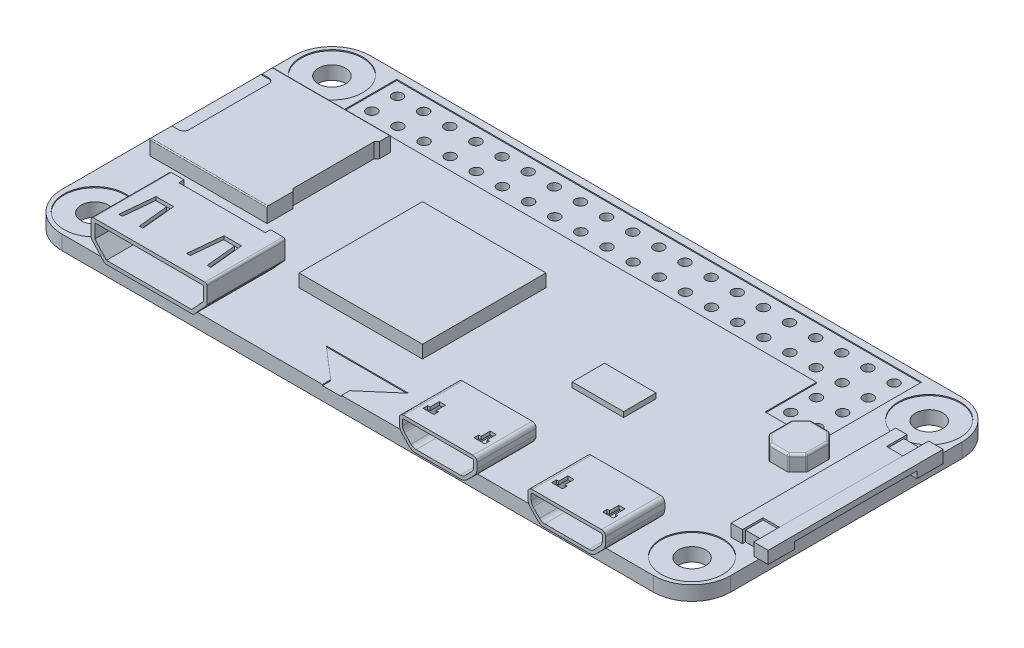
SolidWorks part; units mm, degrees
ref_plane "Front Plane" through (0, 0, 0) normal (0, 0, 1) x (1, 0, 0)
ref_plane "Top Plane" through (0, 0, 0) normal (0, 1, 0) x (1, 0, 0)
ref_plane "Right Plane" through (0, 0, 0) normal (1, 0, 0) x (0, 0, -1)
sketch "Sketch1" plane through (0, 0, 0) normal (0, 1, 0) x (1, 0, 0)
  line L1 (-28.75, 15) -> (28.75, 15)
  line L2 (-32.5, 11.25) -> (-32.5, -11.25)
  line L3 (-28.75, -15) -> (28.75, -15)
  line L4 (32.5, 11.25) -> (32.5, -11.25)
  line L5 (-32.5, 15) -> (32.5, -15) construction
  line L6 (-32.5, -15) -> (32.5, 15) construction
  arc A0 (-32.5, -11.25) -> (-28.75, -15) centre (-28.75, -11.25) ccw
  arc A1 (28.75, -15) -> (32.5, -11.25) centre (28.75, -11.25) ccw
  arc A2 (28.75, 15) -> (32.5, 11.25) centre (28.75, 11.25) cw
  arc A3 (-28.75, 15) -> (-32.5, 11.25) centre (-28.75, 11.25) ccw
  point P0 (0, 0)
  dimension "D3" = 3.75
  dimension "D1" = 65
  dimension "D2" = 30
extrude "Boss-Extrude1" add sketch "Sketch1" along normal blind 1.4 contours L1 A2 L4 A1 L3 A0 L2 A3
sketch "Sketch2" plane through (0, 1.4, 0) normal (0, 1, 0) x (1, 0, 0)
  line L0 (0, 15) -> (0, -15) construction
  line L1 (-28.75, 15) -> (28.75, 15) construction
  line L2 (-28.75, -15) -> (28.75, -15) construction
  line L3 (-32.5, 0) -> (32.5, 0) construction
  line L4 (-32.5, 11.25) -> (-32.5, -11.25) construction
  line L5 (32.5, 11.25) -> (32.5, -11.25) construction
  circle A0 centre (-29.025, 11.525) radius 1.325
  circle A2 centre (29.025, 11.525) radius 1.325
  circle A3 centre (29.025, -11.525) radius 1.325
  circle A4 centre (-29.025, -11.525) radius 1.325
  dimension "D1" = 2.65
  dimension "D2" = 2.15
  dimension "D3" = 2.15
extrude "Cut-Extrude1" cut sketch "Sketch2" against normal through all
sketch "Sketch3" plane through (0, 1.4, 0) normal (0, 1, 0) x (1, 0, 0)
  line L0 (-24.128, 13) -> (-24.128, 10.5) construction
  line L3 (-28.75, 15) -> (28.75, 15) construction
  line L5 (-32.5, 11.25) -> (-32.5, -11.25) construction
  circle A0 centre (-24.128, 13) radius 0.5
  circle A1 centre (-24.128, 10.5) radius 0.5
  dimension "D1" = 1
  dimension "D3" = 1.5
  dimension "D4" = 7.872
  dimension "D2" = 2.5
extrude "Cut-Extrude2" cut sketch "Sketch3" against normal through all
pattern_linear "LPattern1" count 20 spacing 2.54 along (1, 0, 0) of "Cut-Extrude2"
sketch "Sketch5" plane through (0, 1.4, 0) normal (0, 1, 0) x (1, 0, 0)
  line L0 (21.592, 10.5) -> (21.592, 5.5) construction
  line L1 (24.132, 10.5) -> (24.132, 5.5) construction
  line L2 (24.132, 5.5) -> (21.592, 5.5) construction
  circle A0 centre (21.592, 5.5) radius 0.5
  circle A1 centre (24.132, 5.5) radius 0.5
  circle A2 centre (21.592, 8) radius 0.5
  circle A3 centre (24.132, 8) radius 0.5
  dimension "D1" = 2.5
  dimension "D2" = 1
extrude "Cut-Extrude4" cut sketch "Sketch5" against normal through all
sketch "Sketch4" plane through (0, 1.4, 0) normal (0, 1, 0) x (1, 0, 0)
  line L0 (0, 0) -> (0, 14.3) construction
  line L1 (-24.128, 13) -> (-24.128, 10.5) construction
  line L2 (-25.5, 14.3) -> (25.5, 14.3)
  line L3 (-25.5, 14.3) -> (-25.5, 9.2)
  line L4 (-25.5, 9.2) -> (20.4, 9.2)
  line L5 (25.5, 14.3) -> (25.5, 9.2)
  line L6 (-25.5, 11.75) -> (-24.128, 11.75) construction
  line L7 (20.4, 9.2) -> (25.5, 9.2) construction
  line L8 (-2.5, -15) -> (-2.5, -11.55) construction
  line L9 (25.5, 9.2) -> (25.5, 4.2)
  line L10 (25.5, 4.2) -> (20.4, 4.2)
  line L11 (20.4, 9.2) -> (20.4, 4.2)
  line L12 (-28.75, -15) -> (28.75, -15) construction
  line L13 (-6.5, -11.55) -> (1.5, -11.55)
  line L14 (1.5, -11.55) -> (-1.575, -14.2)
  line L15 (-1.575, -14.2) -> (-1.575, -15)
  line L16 (-1.575, -15) -> (-3.425, -15)
  line L17 (-3.425, -15) -> (-3.425, -14.2)
  line L18 (-3.425, -14.2) -> (-6.5, -11.55)
  line L19 (-32.5, 11.25) -> (-32.5, -11.25) construction
  circle A0 centre (-29.025, 11.525) radius 3
  circle A1 centre (-29.025, -11.525) radius 3
  circle A2 centre (29.025, -11.525) radius 3
  circle A3 centre (29.025, 11.525) radius 3
  point P23 (-24.128, 11.75)
  point P26 (-25.5, 11.75)
  dimension "D1" = 6
  dimension "D2" = 5.1
  dimension "D3" = 51
  dimension "D4" = 5.1
  dimension "D5" = 5
  dimension "D6" = 8
  dimension "D7" = 1.85
  dimension "D8" = 3.45
  dimension "D9" = 0.8
  dimension "D10" = 30
extrude "Cut-Extrude3" cut sketch "Sketch4" against normal blind 0.1
sketch "Sketch6" plane through (0, 1.4, 0) normal (0, 1, 0) x (1, 0, 0)
  line L0 (-28.75, -15) -> (-3.425, -15) construction
  line L1 (-12.7, 4) -> (-0.7, 4)
  line L2 (-12.7, 4) -> (-12.7, -8)
  line L3 (-12.7, -8) -> (-0.7, -8)
  line L4 (-0.7, 4) -> (-0.7, -8)
  line L5 (-12.7, 4) -> (-0.7, -8) construction
  line L6 (-12.7, -8) -> (-0.7, 4) construction
  line L7 (-32.5, 11.25) -> (-32.5, -11.25) construction
  point P0 (-6.7, -2)
  dimension "D1" = 12
  dimension "D2" = 7
  dimension "D3" = 19.8
extrude "Boss-Extrude2" add sketch "Sketch6" along normal blind 1.25
sketch "Sketch7" plane through (0, 1.4, 0) normal (0, 1, 0) x (1, 0, 0)
  line L0 (-19.65, 7.85) -> (-19.65, 6.75)
  line L1 (-31.05, 7.85) -> (-19.65, 7.85)
  line L2 (-31.05, 7.85) -> (-31.05, -4.15) construction
  line L3 (-31.05, -4.15) -> (-19.65, -4.15)
  line L4 (-19.65, 7.85) -> (-19.65, -4.15) construction
  line L5 (-19.65, 6.75) -> (-19.9, 6.5)
  line L6 (-19.9, 6.5) -> (-19.9, -1.4)
  line L7 (-19.9, -1.4) -> (-19.65, -1.65)
  line L8 (-19.65, -1.65) -> (-19.65, -4.15)
  line L9 (-31.05, 7.85) -> (-31.05, 6.75)
  line L10 (-31.05, 6.75) -> (-30.4, 6.75)
  line L11 (-29.9, 6.25) -> (-29.9, -1.5)
  line L12 (-30.4, -2) -> (-31.05, -2)
  line L13 (-31.05, -2) -> (-31.05, -4.15)
  line L14 (-28.75, 15) -> (28.75, 15) construction
  line L15 (-32.5, 11.25) -> (-32.5, -11.25) construction
  arc A0 (-29.9, -1.5) -> (-30.4, -2) centre (-30.4, -1.5) cw
  arc A1 (-30.4, 6.75) -> (-29.9, 6.25) centre (-30.4, 6.25) cw
  dimension "D9" = 0.5
  dimension "D1" = 11.4
  dimension "D2" = 12
  dimension "D3" = 2.5
  dimension "D4" = 1.1
  dimension "D5" = 0.25
  dimension "D6" = 1.1
  dimension "D7" = 2.15
  dimension "D8" = 1.15
  dimension "D10" = 7.15
  dimension "D11" = 1.45
extrude "Boss-Extrude3" add sketch "Sketch7" along normal blind 1.45
fillet "Fillet2" radius 0.1 2 edges at (-25.35, 2.85, -7.85) (-25.35, 2.85, 4.15)
sketch "Sketch8" plane through (-29.9, 0, 0) normal (-1, 0, 0) x (0, 0, 1)
  line L0 (-7.85, 2.75) -> (-7.85, 1.4) construction
  line L1 (-7.75, 2.75) -> (4.05, 2.75)
  line L2 (-7.75, 2.75) -> (-7.75, 1.5)
  line L3 (-7.75, 1.5) -> (4.05, 1.5)
  line L4 (4.05, 2.75) -> (4.05, 1.5)
  line L5 (-6.25, 2.85) -> (1.5, 2.85) construction
  line L6 (4.15, 2.75) -> (4.15, 1.4) construction
  line L7 (-6.25, 1.4) -> (1.5, 1.4) construction
  dimension "D1" = 0.1
  dimension "D2" = 0.1
  dimension "D3" = 0.1
  dimension "D4" = 0.1
extrude "Cut-Extrude5" cut sketch "Sketch8" against normal blind 9.5 and the other way through all
sketch "Sketch9" plane through (0, 0, 15) normal (0, 0, 1) x (1, 0, 0)
  line L0 (-19.875, 1.4) -> (-19.875, 4.7) construction
  line L1 (-28.75, 1.4) -> (-3.425, 1.4) construction
  line L2 (-25.5, 4.7) -> (-14.25, 4.7)
  line L3 (-14.25, 4.7) -> (-14.25, 2.85)
  line L4 (-14.25, 2.85) -> (-15.575, 1.4)
  line L5 (-12.7, 1.4) -> (-0.7, 1.4) construction
  line L6 (-15.575, 1.4) -> (-24.175, 1.4)
  line L7 (-24.175, 1.4) -> (-25.5, 2.85)
  line L8 (-25.5, 2.85) -> (-25.5, 4.7)
  line L9 (-32.5, 1.4) -> (-32.5, 0) construction
  dimension "D1" = 3.3
  dimension "D2" = 1.85
  dimension "D3" = 8.6
  dimension "D4" = 11.25
  dimension "D5" = 7
extrude "Boss-Extrude4" add sketch "Sketch9" along normal blind 0.4 and the other way blind 7.2 separate body
fillet "Fillet1" radius 0.2 6 edges at (-15.575, 1.4, 11.6) (-24.175, 1.4, 11.6) (-25.5, 2.85, 11.6) (-14.25, 2.85, 11.6) (-25.5, 4.7, 11.6) (-14.25, 4.7, 11.6)
sketch "Sketch10" plane through (0, 0, 15.4) normal (0, 0, 1) x (1, 0, 0)
  line L12 (-25.15, 4.35) -> (-25.15, 2.9858)
  line L13 (-25.15, 2.9858) -> (-24.0207, 1.75)
  line L14 (-24.0207, 1.75) -> (-15.7293, 1.75)
  line L15 (-15.7293, 1.75) -> (-14.6, 2.9858)
  line L16 (-14.6, 2.9858) -> (-14.6, 4.35)
  line L17 (-14.6, 4.35) -> (-25.15, 4.35)
  line L18 (-25.15, 4.35) -> (-25.15, 2.9858)
  line L19 (-25.15, 2.9858) -> (-24.0207, 1.75)
  line L20 (-24.0207, 1.75) -> (-15.7293, 1.75)
  line L21 (-15.7293, 1.75) -> (-14.6, 2.9858)
  line L22 (-14.6, 2.9858) -> (-14.6, 4.35)
  line L23 (-14.6, 4.35) -> (-25.15, 4.35)
  dimension "D1" = 0.35
extrude "Cut-Extrude6" cut sketch "Sketch10" against normal blind 7
sketch "Sketch11" plane through (0, 0, 8.4) normal (0, 0, 1) x (1, 0, 0)
  line L0 (-19.875, 3.5) -> (-19.875, 1.75) construction
  line L1 (-23.375, 2.95) -> (-16.375, 2.95)
  line L2 (-23.375, 2.95) -> (-23.375, 3.5)
  line L3 (-23.375, 3.5) -> (-16.375, 3.5)
  line L4 (-16.375, 2.95) -> (-16.375, 3.5)
  line L5 (-24.0207, 1.75) -> (-15.7293, 1.75) construction
  line L6 (-24.0207, 1.75) -> (-15.7293, 1.75) construction
  dimension "D1" = 7
  dimension "D2" = 0.55
  dimension "D3" = 1.2
extrude "Boss-Extrude5" add sketch "Sketch11" along normal blind 3.5
sketch "Sketch12" plane through (0, 4.35, 0) normal (0, -1, 0) x (1, 0, 0)
  line L0 (-19.875, 7.8) -> (-19.875, 15.4) construction
  line L1 (-14.45, 7.8) -> (-25.3, 7.8) construction
  line L2 (-14.45, 15.4) -> (-25.3, 15.4) construction
  line L3 (-23.175, 10.57) -> (-23.175, 13.4458) construction
  line L4 (-24.025, 10.57) -> (-22.325, 10.57)
  line L5 (-22.325, 10.57) -> (-22, 13.87)
  line L6 (-22, 13.87) -> (-22.3517, 13.87)
  line L7 (-22.3517, 13.87) -> (-22.6422, 10.92)
  line L8 (-22.6422, 10.92) -> (-23.7078, 10.92)
  line L9 (-23.9983, 13.87) -> (-23.7078, 10.92)
  line L10 (-24.35, 13.87) -> (-23.9983, 13.87)
  line L11 (-24.025, 10.57) -> (-24.35, 13.87)
  line L12 (-16.575, 10.57) -> (-16.575, 13.4458) construction
  line L13 (-15.725, 10.57) -> (-15.4, 13.87)
  line L14 (-15.4, 13.87) -> (-15.7517, 13.87)
  line L15 (-15.7517, 13.87) -> (-16.0422, 10.92)
  line L16 (-17.1078, 10.92) -> (-16.0422, 10.92)
  line L17 (-17.3983, 13.87) -> (-17.1078, 10.92)
  line L18 (-17.75, 13.87) -> (-17.3983, 13.87)
  line L19 (-17.425, 10.57) -> (-17.75, 13.87)
  line L20 (-15.725, 10.57) -> (-17.425, 10.57)
  point P15 (-23.175, 10.92)
  point P28 (-16.575, 10.92)
  dimension "D1" = 0.35
  dimension "D2" = 0.35
  dimension "D3" = 3.3
  dimension "D4" = 2.35
  dimension "D5" = 1.7
  dimension "D6" = 2.77
  dimension "D7" = 4.25
extrude "Cut-Extrude7" cut sketch "Sketch12" against normal through all
sketch "Sketch13" plane through (0, 0, 7.8) normal (0, 0, -1) x (-1, 0, 0)
  line L0 (14.45, 4.7) -> (25.3, 4.7) construction
  line L1 (15.675, 4.7) -> (24.075, 4.7)
  line L2 (15.675, 4.7) -> (15.675, 3.3)
  line L3 (15.675, 3.3) -> (24.075, 3.3)
  line L4 (24.075, 4.7) -> (24.075, 3.3)
  line L5 (19.875, 1.4) -> (19.875, 4.7) construction
  line L6 (24.0868, 1.4) -> (15.6632, 1.4) construction
  dimension "D1" = 8.4
  dimension "D2" = 1.4
extrude "Cut-Extrude8" cut sketch "Sketch13" against normal blind 0.5
sketch "Sketch15" plane through (0, 0, 15) normal (0, 0, 1) x (1, 0, 0)
  line L0 (21.575, 1.4) -> (21.575, 4) construction
  line L1 (-1.575, 1.4) -> (28.75, 1.4) construction
  line L2 (18.2, 4) -> (24.95, 4)
  line L3 (25.35, 3.6) -> (25.35, 3.0523)
  line L4 (25.0714, 2.3598) -> (24.4452, 1.7075)
  line L5 (23.7238, 1.4) -> (19.4262, 1.4)
  line L6 (32.5, 1.4) -> (32.5, 0) construction
  line L7 (18.0786, 2.3598) -> (18.7048, 1.7075)
  line L8 (17.8, 3.6) -> (17.8, 3.0523)
  line L9 (15.325, 0) -> (15.325, 5.5788) construction
  line L10 (-28.75, 0) -> (28.75, 0) construction
  line L11 (9.075, 1.4) -> (9.075, 4) construction
  line L12 (12.85, 3.6) -> (12.85, 3.0523)
  line L13 (12.5714, 2.3598) -> (11.9452, 1.7075)
  line L14 (6.9262, 1.4) -> (11.2238, 1.4)
  line L15 (5.5786, 2.3598) -> (6.2048, 1.7075)
  line L16 (5.3, 3.6) -> (5.3, 3.0523)
  line L17 (12.45, 4) -> (5.7, 4)
  arc A0 (24.4452, 1.7075) -> (23.7238, 1.4) centre (23.7238, 2.4) cw
  arc A1 (18.7048, 1.7075) -> (19.4262, 1.4) centre (19.4262, 2.4) ccw
  arc A2 (25.35, 3.0523) -> (25.0714, 2.3598) centre (24.35, 3.0523) cw
  arc A3 (18.0786, 2.3598) -> (17.8, 3.0523) centre (18.8, 3.0523) cw
  arc A4 (24.95, 4) -> (25.35, 3.6) centre (24.95, 3.6) cw
  arc A5 (17.8, 3.6) -> (18.2, 4) centre (18.2, 3.6) cw
  arc A6 (12.85, 3.6) -> (12.45, 4) centre (12.45, 3.6) ccw
  arc A7 (5.7, 4) -> (5.3, 3.6) centre (5.7, 3.6) ccw
  arc A8 (12.5714, 2.3598) -> (12.85, 3.0523) centre (11.85, 3.0523) ccw
  arc A9 (5.3, 3.0523) -> (5.5786, 2.3598) centre (6.3, 3.0523) ccw
  arc A10 (11.9452, 1.7075) -> (11.2238, 1.4) centre (11.2238, 2.4) cw
  arc A11 (6.2048, 1.7075) -> (6.9262, 1.4) centre (6.9262, 2.4) ccw
  point P14 (24.15, 1.4)
  point P17 (19, 1.4)
  point P20 (25.35, 2.65)
  point P23 (17.8, 2.65)
  point P26 (25.35, 4)
  point P29 (17.8, 4)
  point P54 (12.85, 4)
  point P55 (5.3, 4)
  point P56 (12.85, 2.65)
  point P57 (5.3, 2.65)
  point P58 (11.65, 1.4)
  point P59 (6.5, 1.4)
  dimension "D6" = 1
  dimension "D7" = 0.4
  dimension "D1" = 7.55
  dimension "D2" = 2.6
  dimension "D3" = 1.35
  dimension "D4" = 5.15
  dimension "D5" = 7.15
  dimension "D8" = 4.95
extrude "Boss-Extrude6" add sketch "Sketch15" along normal blind 1.25 and the other way blind 4.5
sketch "Sketch16" plane through (0, 0, 16.25) normal (0, 0, 1) x (1, 0, 0)
  line L12 (12.45, 3.68) -> (5.7, 3.68)
  line L13 (5.62, 3.6) -> (5.62, 3.0523)
  line L14 (5.8095, 2.5814) -> (6.4357, 1.9291)
  line L15 (6.9262, 1.72) -> (11.2238, 1.72)
  line L16 (11.7143, 1.9291) -> (12.3405, 2.5814)
  line L17 (12.53, 3.0523) -> (12.53, 3.6)
  line L18 (12.45, 3.68) -> (5.7, 3.68)
  line L19 (5.62, 3.6) -> (5.62, 3.0523)
  line L20 (5.8095, 2.5814) -> (6.4357, 1.9291)
  line L21 (6.9262, 1.72) -> (11.2238, 1.72)
  line L22 (11.7143, 1.9291) -> (12.3405, 2.5814)
  line L23 (12.53, 3.0523) -> (12.53, 3.6)
  line L30 (24.2143, 1.9291) -> (24.8405, 2.5814)
  line L31 (25.03, 3.0523) -> (25.03, 3.6)
  line L32 (24.95, 3.68) -> (18.2, 3.68)
  line L33 (18.12, 3.6) -> (18.12, 3.0523)
  line L34 (18.3095, 2.5814) -> (18.9357, 1.9291)
  line L35 (19.4262, 1.72) -> (23.7238, 1.72)
  line L36 (24.2143, 1.9291) -> (24.8405, 2.5814)
  line L37 (25.03, 3.0523) -> (25.03, 3.6)
  line L38 (24.95, 3.68) -> (18.2, 3.68)
  line L39 (18.12, 3.6) -> (18.12, 3.0523)
  line L40 (18.3095, 2.5814) -> (18.9357, 1.9291)
  line L41 (19.4262, 1.72) -> (23.7238, 1.72)
  arc A12 (12.53, 3.6) -> (12.45, 3.68) centre (12.45, 3.6) ccw
  arc A13 (5.7, 3.68) -> (5.62, 3.6) centre (5.7, 3.6) ccw
  arc A14 (5.62, 3.0523) -> (5.8095, 2.5814) centre (6.3, 3.0523) ccw
  arc A15 (6.4357, 1.9291) -> (6.9262, 1.72) centre (6.9262, 2.4) ccw
  arc A16 (11.2238, 1.72) -> (11.7143, 1.9291) centre (11.2238, 2.4) ccw
  arc A17 (12.3405, 2.5814) -> (12.53, 3.0523) centre (11.85, 3.0523) ccw
  arc A18 (12.53, 3.6) -> (12.45, 3.68) centre (12.45, 3.6) ccw
  arc A19 (5.7, 3.68) -> (5.62, 3.6) centre (5.7, 3.6) ccw
  arc A20 (5.62, 3.0523) -> (5.8095, 2.5814) centre (6.3, 3.0523) ccw
  arc A21 (6.4357, 1.9291) -> (6.9262, 1.72) centre (6.9262, 2.4) ccw
  arc A22 (11.2238, 1.72) -> (11.7143, 1.9291) centre (11.2238, 2.4) ccw
  arc A23 (12.3405, 2.5814) -> (12.53, 3.0523) centre (11.85, 3.0523) ccw
  arc A30 (23.7238, 1.72) -> (24.2143, 1.9291) centre (23.7238, 2.4) ccw
  arc A31 (24.8405, 2.5814) -> (25.03, 3.0523) centre (24.35, 3.0523) ccw
  arc A32 (25.03, 3.6) -> (24.95, 3.68) centre (24.95, 3.6) ccw
  arc A33 (18.2, 3.68) -> (18.12, 3.6) centre (18.2, 3.6) ccw
  arc A34 (18.12, 3.0523) -> (18.3095, 2.5814) centre (18.8, 3.0523) ccw
  arc A35 (18.9357, 1.9291) -> (19.4262, 1.72) centre (19.4262, 2.4) ccw
  arc A36 (23.7238, 1.72) -> (24.2143, 1.9291) centre (23.7238, 2.4) ccw
  arc A37 (24.8405, 2.5814) -> (25.03, 3.0523) centre (24.35, 3.0523) ccw
  arc A38 (25.03, 3.6) -> (24.95, 3.68) centre (24.95, 3.6) ccw
  arc A39 (18.2, 3.68) -> (18.12, 3.6) centre (18.2, 3.6) ccw
  arc A40 (18.12, 3.0523) -> (18.3095, 2.5814) centre (18.8, 3.0523) ccw
  arc A41 (18.9357, 1.9291) -> (19.4262, 1.72) centre (19.4262, 2.4) ccw
  dimension "D1" = 0.32
  dimension "D2" = 0.32
extrude "Cut-Extrude9" cut sketch "Sketch16" against normal blind 5.25
sketch "Sketch17" plane through (0, 0, 11) normal (0, 0, 1) x (1, 0, 0)
  line L0 (12.85, 3.3262) -> (17.8, 3.3262) construction
  line L1 (12.85, 3.0523) -> (12.85, 3.6) construction
  line L2 (17.8, 3.6) -> (17.8, 3.0523) construction
  line L3 (15.325, 3.3262) -> (15.325, 1.4) construction
  line L4 (11.2238, 1.4) -> (19.4262, 1.4) construction
  line L5 (9.075, 1.72) -> (9.075, 3.68) construction
  line L6 (6.9262, 1.72) -> (11.2238, 1.72) construction
  line L7 (12.45, 3.68) -> (5.7, 3.68) construction
  line L8 (6.9262, 1.72) -> (11.2238, 1.72) construction
  line L9 (7.5, 3.32) -> (10.65, 3.32)
  line L10 (7.5, 3.32) -> (7.5, 2.92)
  line L11 (7.5, 2.92) -> (10.65, 2.92)
  line L12 (10.65, 3.32) -> (10.65, 2.92)
  line L13 (7.5, 3.32) -> (10.65, 2.92) construction
  line L14 (7.5, 2.92) -> (10.65, 3.32) construction
  line L15 (23.15, 2.92) -> (20, 3.32) construction
  line L16 (23.15, 3.32) -> (20, 2.92) construction
  line L17 (20, 3.32) -> (20, 2.92)
  line L18 (23.15, 2.92) -> (20, 2.92)
  line L19 (23.15, 3.32) -> (23.15, 2.92)
  line L20 (23.15, 3.32) -> (20, 3.32)
  point P16 (9.075, 3.12)
  point P27 (21.575, 3.12)
  dimension "D1" = 3.15
  dimension "D2" = 0.4
  dimension "D3" = 1.4
extrude "Boss-Extrude7" add sketch "Sketch17" along normal blind 3.5
sketch "Sketch18" plane through (0, 4, 0) normal (0, 1, 0) x (1, 0, 0)
  line L0 (9.075, -16.25) -> (9.075, -10.5) construction
  line L1 (12.45, -16.25) -> (5.7, -16.25) construction
  line L2 (6.9262, -10.5) -> (11.2238, -10.5) construction
  line L3 (12.85, -16.25) -> (17.8, -16.25) construction
  line L4 (15.325, -16.25) -> (15.325, -10.5) construction
  line L5 (6.6, -13.37) -> (6.6, -14.72) construction
  line L6 (6.9, -13.37) -> (6.3, -13.37)
  line L7 (6.3, -13.37) -> (6.3, -14.27)
  line L8 (6.3, -14.27) -> (6.075, -14.27)
  line L9 (6.075, -14.27) -> (6.075, -14.72)
  line L10 (6.075, -14.72) -> (7.125, -14.72)
  line L11 (7.125, -14.27) -> (7.125, -14.72)
  line L12 (6.9, -14.27) -> (7.125, -14.27)
  line L13 (6.9, -13.37) -> (6.9, -14.27)
  line L14 (11.55, -13.37) -> (11.55, -14.72) construction
  line L15 (11.25, -13.37) -> (11.25, -14.27)
  line L16 (11.25, -14.27) -> (11.025, -14.27)
  line L17 (11.025, -14.27) -> (11.025, -14.72)
  line L18 (12.075, -14.72) -> (11.025, -14.72)
  line L19 (12.075, -14.27) -> (12.075, -14.72)
  line L20 (11.85, -14.27) -> (12.075, -14.27)
  line L21 (11.85, -13.37) -> (11.85, -14.27)
  line L22 (11.25, -13.37) -> (11.85, -13.37)
  line L23 (19.1, -13.37) -> (19.1, -14.72) construction
  line L24 (24.05, -13.37) -> (24.05, -14.72) construction
  line L25 (21.575, -16.25) -> (21.575, -10.5) construction
  line L26 (19.4, -13.37) -> (18.8, -13.37)
  line L27 (18.8, -13.37) -> (18.8, -14.27)
  line L28 (18.8, -14.27) -> (18.575, -14.27)
  line L29 (18.575, -14.27) -> (18.575, -14.72)
  line L30 (18.575, -14.72) -> (19.625, -14.72)
  line L31 (19.625, -14.27) -> (19.625, -14.72)
  line L32 (19.4, -14.27) -> (19.625, -14.27)
  line L33 (19.4, -13.37) -> (19.4, -14.27)
  line L34 (23.75, -13.37) -> (23.75, -14.27)
  line L35 (23.75, -14.27) -> (23.525, -14.27)
  line L36 (23.525, -14.27) -> (23.525, -14.72)
  line L37 (24.575, -14.72) -> (23.525, -14.72)
  line L38 (24.575, -14.27) -> (24.575, -14.72)
  line L39 (24.35, -14.27) -> (24.575, -14.27)
  line L40 (24.35, -13.37) -> (24.35, -14.27)
  line L41 (23.75, -13.37) -> (24.35, -13.37)
  dimension "D1" = 1.05
  dimension "D2" = 1.35
  dimension "D3" = 0.9
  dimension "D4" = 0.6
  dimension "D5" = 3.9
  dimension "D6" = 1.53
extrude "Cut-Extrude10" cut sketch "Sketch18" against normal up to surface (0.32 mm away) up to face at (9.075, 3.68, 13.625)
sketch "Sketch19" plane through (32.5, 0, 0) normal (1, 0, 0) x (0, 0, -1)
  line L0 (0, 1.4) -> (0, 2.6) construction
  line L1 (11.25, 1.4) -> (-11.25, 1.4) construction
  line L2 (-8.5, 2.6) -> (8.5, 2.6)
  line L3 (8.5, 2.6) -> (8.5, 1.4)
  line L4 (6.5, 1.4) -> (6.75, 1.4) construction
  line L5 (8.5, 1.4) -> (5.95, 1.4)
  line L6 (-1.4, 1.4) -> (6.5, 1.4) construction
  line L7 (5.95, 1.4) -> (5.95, 2.05)
  line L8 (5.95, 2.05) -> (-5.95, 2.05)
  line L9 (-5.95, 2.05) -> (-5.95, 1.4)
  line L10 (-5.95, 1.4) -> (-8.5, 1.4)
  line L11 (-8, 1.4) -> (4, 1.4) construction
  line L12 (-8.5, 1.4) -> (-8.5, 2.6)
  line L13 (15, 1.4) -> (15, 0) construction
  dimension "D1" = 1.2
  dimension "D2" = 0.55
  dimension "D3" = 11.9
  dimension "D4" = 17
  dimension "D5" = 6.5
extrude "Boss-Extrude8" add sketch "Sketch19" along normal blind 0.9 and the other way blind 0.5
sketch "Sketch20" plane through (0, 1.4, 0) normal (0, 1, 0) x (1, 0, 0)
  line L0 (33.4, 0) -> (29.3, 0) construction
  line L1 (33.4, 8.5) -> (33.4, -8.5) construction
  line L2 (32, 6) -> (30.4, 6)
  line L3 (32, 8.5) -> (32, -8.5) construction
  line L4 (30.4, 6) -> (30.4, 8)
  line L5 (30.4, 8) -> (29.3, 8)
  line L6 (29.3, 8) -> (29.3, -8)
  line L7 (29.3, -8) -> (30.4, -8)
  line L8 (30.4, -8) -> (30.4, -6)
  line L9 (30.4, -6) -> (32, -6)
  line L10 (32, -6) -> (32, 6)
  dimension "D1" = 16
  dimension "D2" = 2.7
  dimension "D3" = 1.1
  dimension "D4" = 12
extrude "Boss-Extrude9" add sketch "Sketch20" along normal blind 1.19
sketch "Sketch21" plane through (0, 1.4, 0) normal (0, 1, 0) x (1, 0, 0)
  line L0 (32, 6) -> (32, 8.5) construction
  line L1 (30.4, 6) -> (32, 6)
  line L2 (30.4, 6) -> (30.4, 7.7)
  line L3 (30.4, 7.7) -> (32, 7.7)
  line L4 (32, 6) -> (32, 7.7)
  line L5 (32, 8.5) -> (32, -8.5) construction
  line L6 (30.4, -6) -> (32, -6)
  line L7 (30.4, -6) -> (30.4, -7.7)
  line L8 (30.4, -7.7) -> (32, -7.7)
  line L9 (32, -6) -> (32, -7.7)
  dimension "D1" = 1.7
extrude "Boss-Extrude10" add sketch "Sketch21" along normal blind 1
sketch "Sketch22" plane through (0, 1.4, 0) normal (0, 1, 0) x (1, 0, 0)
  line L0 (32.5, -8.5) -> (32.5, -11.25) construction
  line L1 (23.85, 4.25) -> (27.5, 4.25)
  line L2 (23.85, 4.25) -> (23.85, 0.25)
  line L3 (23.85, 0.25) -> (27.5, 0.25)
  line L4 (27.5, 4.25) -> (27.5, 0.25)
  line L5 (-28.75, 15) -> (28.75, 15) construction
  dimension "D1" = 3.65
  dimension "D2" = 4
  dimension "D3" = 5
  dimension "D4" = 10.75
extrude "Boss-Extrude11" add sketch "Sketch22" along normal blind 1.5
chamfer "Chamfer1" distance 0.9 angle 45 4 edges at (23.85, 2.15, -4.25) (27.5, 2.15, -4.25) (27.5, 2.15, -0.25) (23.85, 2.15, -0.25)
sketch "Sketch23" plane through (0, 1.4, 0) normal (0, 1, 0) x (1, 0, 0)
  line L0 (-28.75, 15) -> (28.75, 15) construction
  line L1 (9, 0) -> (14, 0)
  line L2 (9, 0) -> (9, -3.15)
  line L3 (9, -3.15) -> (14, -3.15)
  line L4 (14, 0) -> (14, -3.15)
  line L5 (32.5, -8.5) -> (32.5, -11.25) construction
  dimension "D1" = 5
  dimension "D2" = 3.15
  dimension "D3" = 15
  dimension "D4" = 18.5
extrude "Boss-Extrude12" add sketch "Sketch23" along normal blind 0.5
fillet "Fillet3" radius 0.2 16 edges at (27.05, 2.9, -3.8) (27.5, 2.9, -2.25) (27.05, 2.9, -0.7) (25.675, 2.9, -0.25) (24.3, 2.9, -0.7) (23.85, 2.9, -2.25) (24.3, 2.9, -3.8) (25.675, 2.9, -4.25) (26.6, 2.15, -4.25) (24.75, 2.15, -4.25) (23.85, 2.15, -3.35) (24.75, 2.15, -0.25) (23.85, 2.15, -1.15) (27.5, 2.15, -3.35) (27.5, 2.15, -1.15) (26.6, 2.15, -0.25)
